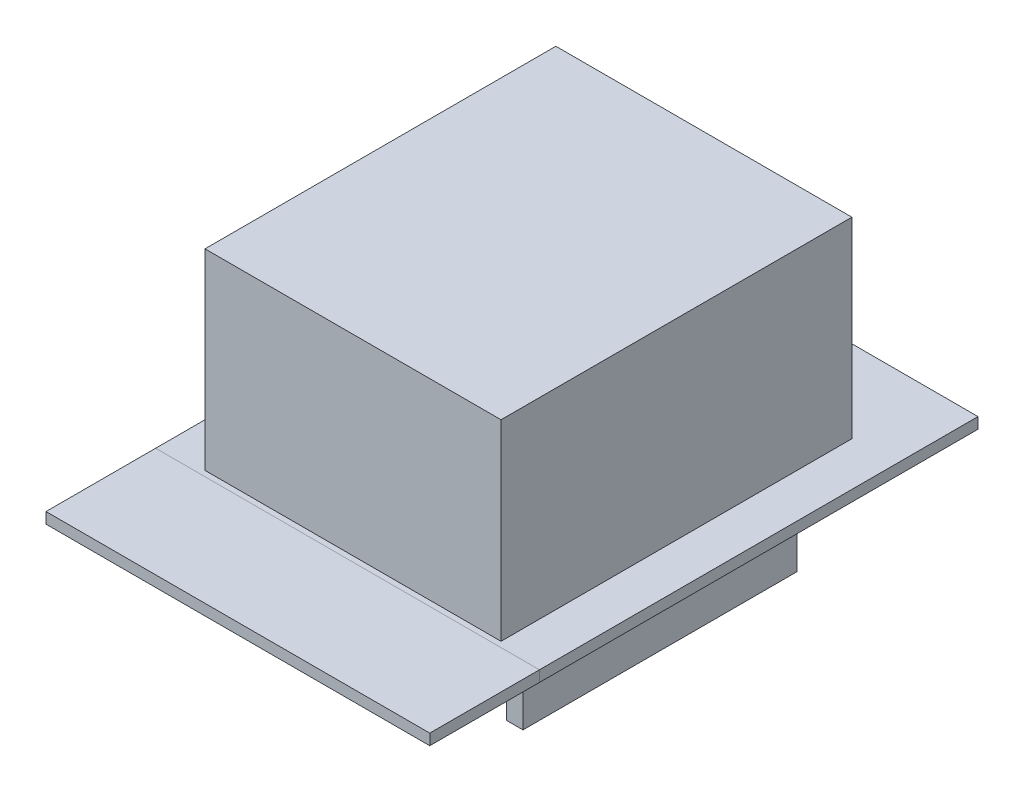
SolidWorks part; units mm, degrees
ref_plane "Front Plane" through (0, 0, 0) normal (0, 0, 1) x (1, 0, 0)
ref_plane "Top Plane" through (0, 0, 0) normal (0, 1, 0) x (1, 0, 0)
ref_plane "Right Plane" through (0, 0, 0) normal (1, 0, 0) x (0, 0, -1)
sketch "Sketch1" plane through (0, 0, 0) normal (0, 1, 0) x (1, 0, 0)
  line L1 (-76.1915, 102.4862) -> (-6.1915, 102.4862)
  line L2 (-76.1915, 102.4862) -> (-76.1915, 22.4862)
  line L3 (-76.1915, 22.4862) -> (-6.1915, 22.4862)
  line L4 (-6.1915, 102.4862) -> (-6.1915, 22.4862)
  dimension "D1" = 70
  dimension "D2" = 80
extrude "Boss-Extrude1" add sketch "Sketch1" along normal blind 2
sketch "Sketch2" plane through (0, 2, 0) normal (0, 1, 0) x (1, 0, 0)
  line L0 (-76.1915, 102.4862) -> (-76.1915, 22.4862) construction
  line L1 (-68.1915, 87.4862) -> (-14.1915, 87.4862)
  line L2 (-68.1915, 87.4862) -> (-68.1915, 23.4862)
  line L3 (-68.1915, 23.4862) -> (-14.1915, 23.4862)
  line L4 (-14.1915, 87.4862) -> (-14.1915, 23.4862)
  line L5 (-6.1915, 22.4862) -> (-6.1915, 102.4862) construction
  line L6 (-76.1915, 22.4862) -> (-6.1915, 22.4862) construction
  line L7 (-6.1915, 102.4862) -> (-76.1915, 102.4862) construction
  dimension "D1" = 8
  dimension "D2" = 8
  dimension "D3" = 1
  dimension "D4" = 15
extrude "Boss-Extrude2" add sketch "Sketch2" along normal blind 35
sketch "Sketch3" plane through (0, 0, -22.4862) normal (0, 0, 1) x (1, 0, 0)
  line L1 (-76.1915, 0) -> (-6.1915, 0)
  line L2 (-76.1915, 0) -> (-76.1915, 2)
  line L3 (-76.1915, 2) -> (-6.1915, 2)
  line L4 (-6.1915, 0) -> (-6.1915, 2)
  line L5 (-9.1915, 0) -> (-12.1915, 0)
  line L6 (-9.1915, 0) -> (-9.1915, -9)
  line L7 (-9.1915, -9) -> (-12.1915, -9)
  line L8 (-12.1915, 0) -> (-12.1915, -9)
  line L9 (-73.1915, 0) -> (-70.1915, 0)
  line L10 (-73.1915, 0) -> (-73.1915, -9)
  line L11 (-73.1915, -9) -> (-70.1915, -9)
  line L12 (-70.1915, 0) -> (-70.1915, -9)
  line M1 (-76.1915, 0) -> (-6.1915, 0)
  line M2 (-6.1915, 0) -> (-6.1915, 2)
  line M3 (-6.1915, 2) -> (-76.1915, 2)
  line M4 (-76.1915, 2) -> (-76.1915, 0)
  dimension "D1" = 3
  dimension "D2" = 3
  dimension "D3" = 9
  dimension "D4" = 3
extrude "Boss-Extrude3" add sketch "Sketch3" along normal blind 20 separate body contours L1 M4 M1 M2 M3 region at (-41.1915, 1, -22.4862)
extrude "Boss-Extrude4" add sketch "Sketch3<3>" against normal blind 50 separate body contours L12 L1 L10 L11 | L1 L8 L7 L6 region at (-71.6915, -4.5, -22.4862) region at (-10.6915, -4.5, -22.4862)
sketch "Sketch3<3>" plane through (0, 0, -22.4862) normal (0, 0, 1) x (1, 0, 0) same geometry as "Sketch3"
